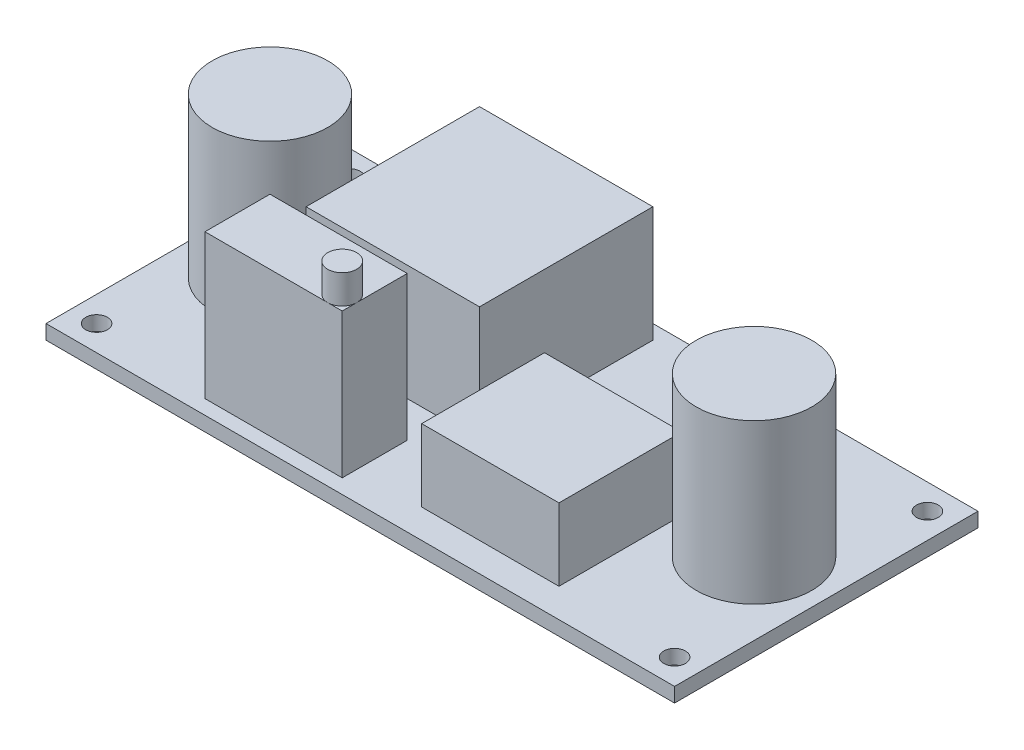
SolidWorks part; units mm, degrees
ref_plane "Front" through (0, 0, 0) normal (0, 0, 1) x (1, 0, 0)
ref_plane "Top" through (0, 0, 0) normal (0, 1, 0) x (1, 0, 0)
ref_plane "Right" through (0, 0, 0) normal (1, 0, 0) x (0, 0, -1)
sketch "Эскиз1" plane through (0, 0, 0) normal (0, 1, 0) x (1, 0, 0)
  line L0 (-21.75, 0) -> (21.75, 0) construction
  line L1 (-21.75, 10.5) -> (21.75, 10.5)
  line L2 (-21.75, 10.5) -> (-21.75, -10.5)
  line L3 (-21.75, -10.5) -> (21.75, -10.5)
  line L4 (21.75, 10.5) -> (21.75, -10.5)
  line L5 (-21.75, 10.5) -> (21.75, -10.5) construction
  line L6 (-21.75, -10.5) -> (21.75, 10.5) construction
  line L7 (0, 10.5) -> (0, -10.5) construction
  line L9 (2.25, 0) -> (11.75, 0)
  line L10 (2.25, 0) -> (2.25, -8.5)
  line L11 (2.25, -8.5) -> (11.75, -8.5)
  line L12 (11.75, 0) -> (11.75, -8.5)
  line L13 (-11.75, -5) -> (-2.25, -5)
  line L14 (-11.75, -5) -> (-11.75, -9.5)
  line L15 (-11.75, -9.5) -> (-2.25, -9.5)
  line L16 (-2.25, -5) -> (-2.25, -9.5)
  line L17 (0.25, 9.5) -> (-11.75, 9.5)
  line L18 (0.25, 9.5) -> (0.25, -2.5)
  line L19 (0.25, -2.5) -> (-11.75, -2.5)
  line L20 (-11.75, 9.5) -> (-11.75, -2.5)
  circle A0 centre (-15, 7.75) radius 1.75
  circle A1 centre (15, -7.75) radius 1.75
  circle A2 centre (-20, 8.75) radius 0.75
  circle A3 centre (20, 8.75) radius 0.75
  circle A4 centre (20, -8.75) radius 0.75
  circle A5 centre (-20, -8.75) radius 0.75
  circle A6 centre (-16.75, 0) radius 4
  circle A7 centre (16.75, 0) radius 4
  point P0 (0, 0)
  dimension "D3" = 3.5
  dimension "D4" = 2.75
  dimension "D6" = 6.75
  dimension "D8" = 1.5
  dimension "D9" = 1.75
  dimension "D10" = 1.75
  dimension "D11" = 8
  dimension "D1" = 21
  dimension "D2" = 43.5
  dimension "D5" = 2.75
  dimension "D7" = 6.75
  dimension "D12" = 5
  dimension "D13" = 12
  dimension "D14" = 1
  dimension "D15" = 10
  dimension "D16" = 4.5
  dimension "D17" = 9.5
  dimension "D18" = 1
  dimension "D19" = 10
  dimension "D20" = 9.5
  dimension "D21" = 8.5
  dimension "D22" = 2
  dimension "D23" = 10
extrude "Бобышка-Вытянуть1" add sketch "Эскиз1" against normal blind 1 contours A6 | L4 L1 L2 L3 A7 A6 A5 A4 A3 A2 A1 A0 L20 L17 L18 L19 L9 L12 L11 L10 L13 L16 L15 L14 | L17 L20 L19 L18 | L16 L13 L14 L15 | L12 L9 L10 L11 | A1 | A7 | A0 region at (1.0825, 0, -0.2872) region at (7, 0, 4.25) region at (-7, 0, 7.25) region at (-5.75, 0, -3.5) region at (-15, 0, -7.75) region at (15, 0, 7.75) region at (-16.75, 0, 0) region at (16.75, 0, 0)
extrude "Бобышка-Вытянуть2" add sketch "Эскиз1<3>" along normal blind 11 contours A6 | A7 region at (-16.75, 0, 0) region at (16.75, 0, 0)
sketch "Эскиз1<3>" plane through (0, 0, 0) normal (0, 1, 0) x (1, 0, 0) same geometry as "Эскиз1"
extrude "Бобышка-Вытянуть3" add sketch "Эскиз1<4>" along normal blind 5 contours L12 L9 L10 L11 region at (7, 0, 4.25)
sketch "Эскиз1<4>" plane through (0, 0, 0) normal (0, 1, 0) x (1, 0, 0) same geometry as "Эскиз1"
extrude "Бобышка-Вытянуть4" add sketch "Эскиз1<5>" along normal blind 10 contours L16 L13 L14 L15 region at (-7, 0, 7.25)
sketch "Эскиз1<5>" plane through (0, 0, 0) normal (0, 1, 0) x (1, 0, 0) same geometry as "Эскиз1"
extrude "Бобышка-Вытянуть5" add sketch "Эскиз1<6>" along normal blind 8 contours L17 L20 L19 L18 region at (-5.75, 0, -3.5)
sketch "Эскиз1<6>" plane through (0, 0, 0) normal (0, 1, 0) x (1, 0, 0) same geometry as "Эскиз1"
sketch "Эскиз2" plane through (0, 10, 0) normal (0, 1, 0) x (1, 0, 0)
  line L0 (-2.25, -5) -> (-2.25, -9.5) construction
  line L1 (-11.75, -9.5) -> (-2.25, -9.5) construction
  circle A0 centre (-3.25, -8.5) radius 1
  dimension "D1" = 2
extrude "Бобышка-Вытянуть6" add sketch "Эскиз2" along normal blind 2
